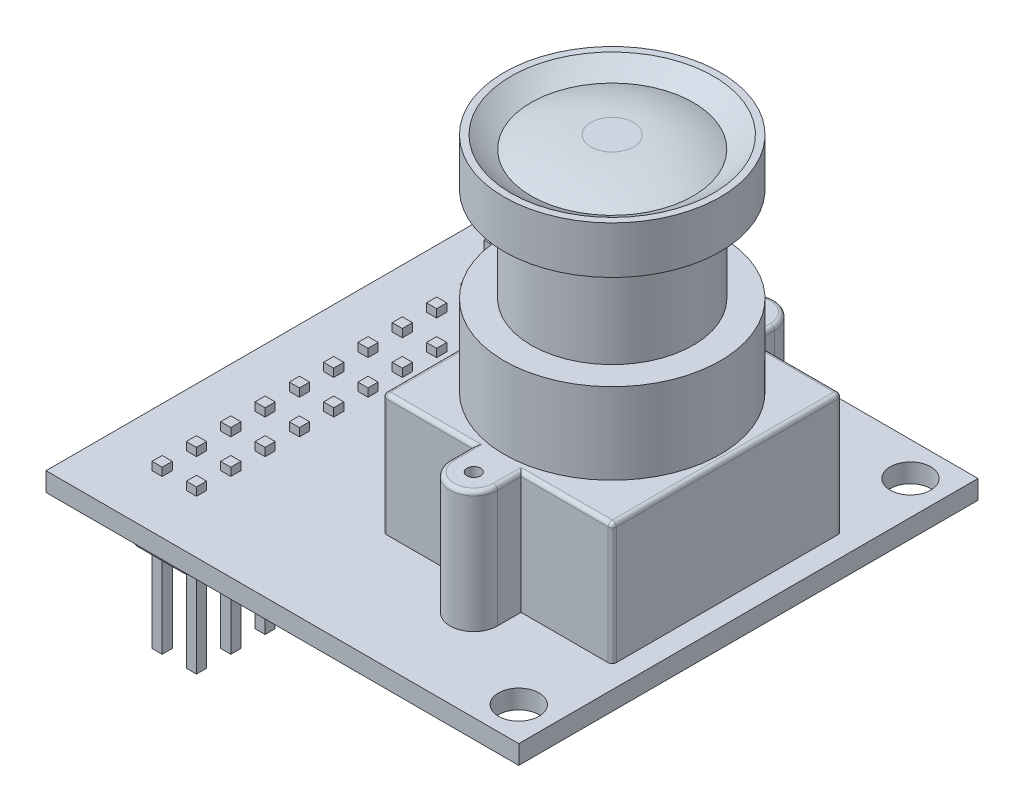
SolidWorks part; units mm, degrees
ref_plane "Front Plane" through (0, 0, 0) normal (0, 0, 1) x (1, 0, 0)
ref_plane "Top Plane" through (0, 0, 0) normal (0, 1, 0) x (1, 0, 0)
ref_plane "Right Plane" through (0, 0, 0) normal (1, 0, 0) x (0, 0, -1)
sketch "Sketch1" plane through (0, 0, 0) normal (0, 1, 0) x (1, 0, 0)
  line L1 (-19.2335, 8.5) -> (15.7665, 8.5)
  line L2 (-19.2335, 8.5) -> (-19.2335, -25.5)
  line L3 (-19.2335, -25.5) -> (15.7665, -25.5)
  line L4 (15.7665, 8.5) -> (15.7665, -25.5)
  circle A2 centre (13.2665, 6) radius 1.5
  circle A3 centre (13.2665, -23) radius 1.5
  dimension "D1" = 35
  dimension "D2" = 34
  dimension "D6" = 2.5
  dimension "D7" = 2.5
  dimension "D8" = 2.5
  dimension "D9" = 2.5
extrude "Boss-Extrude1" add sketch "Sketch1" along normal blind 1.4
sketch "Sketch2" plane through (0, 1.4, 0) normal (0, 1, 0) x (1, 0, 0)
  line L0 (15.7665, -25.5) -> (15.7665, 8.5) construction
  line L1 (-2.8135, 0) -> (3.9365, 0)
  line L2 (-2.8135, 0) -> (-2.8135, -17)
  line L3 (-2.8135, -17) -> (3.9365, -17)
  line L4 (14.1865, 0) -> (14.1865, -17)
  line L5 (-19.2335, -25.5) -> (15.7665, -25.5) construction
  line L6 (3.1865, -14.9296) -> (3.1865, -19.9748) construction
  line L7 (8.1865, -14.9296) -> (8.1865, -19.9748) construction
  line L8 (3.9365, -18.75) -> (3.9365, -17)
  line L9 (7.4365, -18.75) -> (7.4365, -17)
  line L10 (7.4365, -17) -> (14.1865, -17)
  line L11 (-2.8135, -8.5) -> (14.1865, -8.5) construction
  line L12 (7.4365, 1.75) -> (7.4365, 0)
  line L13 (3.9365, 1.75) -> (3.9365, 0)
  line L14 (7.4365, 0) -> (14.1865, 0)
  arc A0 (3.9365, -18.75) -> (7.4365, -18.75) centre (5.6865, -18.75) ccw
  arc A1 (3.9365, 1.75) -> (7.4365, 1.75) centre (5.6865, 1.75) cw
  circle A2 centre (5.6865, 1.75) radius 0.5
  circle A3 centre (5.6865, -18.75) radius 0.5
  dimension "D7" = 3.5
  dimension "D8" = 1
  dimension "D9" = 1
  dimension "D1" = 17
  dimension "D2" = 17
  dimension "D3" = 1.58
  dimension "D4" = 8.5
  dimension "D5" = 6
  dimension "D6" = 6
  dimension "D10" = 8.5
extrude "Boss-Extrude2" add sketch "Sketch2" along normal blind 9
sketch "Sketch3" plane through (0, 10.4, 0) normal (0, 1, 0) x (1, 0, 0)
  line L0 (5.6865, -8.5) -> (-7.3938, -8.5) construction
  line L1 (-2.8135, 0) -> (-2.8135, -17) construction
  line L2 (-2.8135, -9.5) -> (-2.2507, -9.5)
  line L3 (-2.8135, -9.5) -> (-2.8135, -7.5)
  line L4 (-2.8135, -7.5) -> (-2.2507, -7.5)
  line L6 (7.4365, -17) -> (14.1865, -17) construction
  line L7 (14.1865, 0) -> (7.4365, 0) construction
  arc A0 (-2.2507, -9.5) -> (-2.2507, -7.5) centre (5.6865, -8.5) ccw
  circle A1 centre (5.6865, -18.75) radius 0.5 construction
  dimension "D1" = 16
  dimension "D2" = 1
  dimension "D3" = 8.5
  dimension "D4" = 8.5
  dimension "D5" = 1
  dimension "D6" = 0
extrude "Boss-Extrude3" add sketch "Sketch3" along normal blind 6
sketch "Sketch4" plane through (0, 16.4, 0) normal (0, 1, 0) x (1, 0, 0)
  circle A0 centre (5.6865, -8.5) radius 6
  dimension "D1" = 12
extrude "Boss-Extrude4" add sketch "Sketch4" along normal blind 7
sketch "Sketch5" plane through (0, 23.4, 0) normal (0, 1, 0) x (1, 0, 0)
  circle A0 centre (5.6865, -8.5) radius 8
  dimension "D1" = 16
extrude "Boss-Extrude5" add sketch "Sketch5" along normal blind 3.5
sketch "Sketch6" plane through (0, 26.9, 0) normal (0, 1, 0) x (1, 0, 0)
  circle A0 centre (5.6865, -8.5) radius 7.5
  dimension "D1" = 15
extrude "Cut-Extrude1" cut sketch "Sketch6" against normal blind 2
fillet "Fillet1" radius 10 1 edges at (5.6865, 24.9, 16)
sketch "Sketch7" plane through (0, 24.9, 0) normal (0, 1, 0) x (1, 0, 0)
  circle A0 centre (5.6865, -8.5) radius 6
  dimension "D1" = 12
extrude "Boss-Extrude6" add sketch "Sketch7" along normal blind 2
fillet "Fillet2" radius 11 1 edges at (5.6865, 26.9, 14.5)
fillet "Fillet3" radius 0.3 17 edges at (0.5615, 10.4, 0) (3.9365, 10.4, -0.875) (5.6865, 10.4, -3.5) (7.4365, 10.4, -0.875) (10.8115, 10.4, 0) (14.1865, 10.4, 8.5) (10.8115, 10.4, 17) (7.4365, 10.4, 17.875) (5.6865, 10.4, 20.5) (3.9365, 10.4, 17.875) (0.5615, 10.4, 17) (-2.8135, 10.4, 13.25) (-2.8135, 10.4, 3.75) (-2.8135, 5.9, 0) (-2.8135, 5.9, 17) (14.1865, 5.9, 0) (14.1865, 5.9, 17)
sketch "Sketch8" plane through (-2.8135, 0, 0) normal (-1, 0, 0) x (0, 0, 1)
  line L0 (7.5, 16.4) -> (7.5, 10.1) construction
  line L1 (9.5, 16.4) -> (9.5, 10.1) construction
  line L2 (7.5, 16.4) -> (9.5, 16.4) construction
  circle A0 centre (8.5, 13.9) radius 0.5
  dimension "D1" = 1
  dimension "D2" = 1
  dimension "D3" = 1
  dimension "D4" = 2.5
extrude "Cut-Extrude2" cut sketch "Sketch8" against normal blind 0.5
sketch "Sketch9" plane through (0, 0, 0) normal (0, -1, 0) x (1, 0, 0)
  line L0 (-14.9335, 21.2) -> (-14.9335, 22.1314) construction
  line L1 (-12.0185, 20.825) -> (-12.0185, 21.575)
  line L2 (-14.5585, 20.825) -> (-15.3085, 20.825)
  line L3 (-14.5585, 20.825) -> (-14.5585, 21.575)
  line L4 (-14.5585, 21.575) -> (-15.3085, 21.575)
  line L5 (-15.3085, 20.825) -> (-15.3085, 21.575)
  line L6 (-14.5585, 20.825) -> (-15.3085, 21.575) construction
  line L7 (-14.5585, 21.575) -> (-15.3085, 20.825) construction
  line L8 (-12.0185, 21.575) -> (-12.7685, 21.575)
  line L9 (-12.7685, 20.825) -> (-12.7685, 21.575)
  line L10 (-12.0185, 20.825) -> (-12.7685, 20.825)
  line L11 (-19.2335, -8.5) -> (-19.2335, 25.5) construction
  line L12 (-19.2335, 25.5) -> (15.7665, 25.5) construction
  line L13 (-12.0185, 18.285) -> (-12.0185, 19.035)
  line L14 (-12.0185, 19.035) -> (-12.7685, 19.035)
  line L15 (-12.7685, 18.285) -> (-12.7685, 19.035)
  line L16 (-12.0185, 18.285) -> (-12.7685, 18.285)
  line L17 (-12.0185, 15.745) -> (-12.0185, 16.495)
  line L18 (-12.0185, 16.495) -> (-12.7685, 16.495)
  line L19 (-12.7685, 15.745) -> (-12.7685, 16.495)
  line L20 (-12.0185, 15.745) -> (-12.7685, 15.745)
  line L21 (-12.0185, 13.205) -> (-12.0185, 13.955)
  line L22 (-12.0185, 13.955) -> (-12.7685, 13.955)
  line L23 (-12.7685, 13.205) -> (-12.7685, 13.955)
  line L24 (-12.0185, 13.205) -> (-12.7685, 13.205)
  line L25 (-12.0185, 10.665) -> (-12.0185, 11.415)
  line L26 (-12.0185, 11.415) -> (-12.7685, 11.415)
  line L27 (-12.7685, 10.665) -> (-12.7685, 11.415)
  line L28 (-12.0185, 10.665) -> (-12.7685, 10.665)
  line L29 (-12.0185, 8.125) -> (-12.0185, 8.875)
  line L30 (-12.0185, 8.875) -> (-12.7685, 8.875)
  line L31 (-12.7685, 8.125) -> (-12.7685, 8.875)
  line L32 (-12.0185, 8.125) -> (-12.7685, 8.125)
  line L33 (-12.0185, 5.585) -> (-12.0185, 6.335)
  line L34 (-12.0185, 6.335) -> (-12.7685, 6.335)
  line L35 (-12.7685, 5.585) -> (-12.7685, 6.335)
  line L36 (-12.0185, 5.585) -> (-12.7685, 5.585)
  line L37 (-12.0185, 3.045) -> (-12.0185, 3.795)
  line L38 (-12.0185, 3.795) -> (-12.7685, 3.795)
  line L39 (-12.7685, 3.045) -> (-12.7685, 3.795)
  line L40 (-12.0185, 3.045) -> (-12.7685, 3.045)
  line L41 (-12.0185, 0.505) -> (-12.0185, 1.255)
  line L42 (-12.0185, 1.255) -> (-12.7685, 1.255)
  line L43 (-12.7685, 0.505) -> (-12.7685, 1.255)
  line L44 (-12.0185, 0.505) -> (-12.7685, 0.505)
  line L45 (-12.0185, -2.035) -> (-12.0185, -1.285)
  line L46 (-12.0185, -1.285) -> (-12.7685, -1.285)
  line L47 (-12.7685, -2.035) -> (-12.7685, -1.285)
  line L48 (-12.0185, -2.035) -> (-12.7685, -2.035)
  line L49 (-12.0185, -4.575) -> (-12.0185, -3.825)
  line L50 (-12.0185, -3.825) -> (-12.7685, -3.825)
  line L51 (-12.7685, -4.575) -> (-12.7685, -3.825)
  line L52 (-12.0185, -4.575) -> (-12.7685, -4.575)
  line L53 (-14.5585, 18.285) -> (-14.5585, 19.035)
  line L54 (-14.5585, 19.035) -> (-15.3085, 19.035)
  line L55 (-15.3085, 18.285) -> (-15.3085, 19.035)
  line L56 (-14.5585, 18.285) -> (-15.3085, 18.285)
  line L57 (-14.5585, 15.745) -> (-14.5585, 16.495)
  line L58 (-14.5585, 16.495) -> (-15.3085, 16.495)
  line L59 (-15.3085, 15.745) -> (-15.3085, 16.495)
  line L60 (-14.5585, 15.745) -> (-15.3085, 15.745)
  line L61 (-14.5585, 13.205) -> (-14.5585, 13.955)
  line L62 (-14.5585, 13.955) -> (-15.3085, 13.955)
  line L63 (-15.3085, 13.205) -> (-15.3085, 13.955)
  line L64 (-14.5585, 13.205) -> (-15.3085, 13.205)
  line L65 (-14.5585, 10.665) -> (-14.5585, 11.415)
  line L66 (-14.5585, 11.415) -> (-15.3085, 11.415)
  line L67 (-15.3085, 10.665) -> (-15.3085, 11.415)
  line L68 (-14.5585, 10.665) -> (-15.3085, 10.665)
  line L69 (-14.5585, 8.125) -> (-14.5585, 8.875)
  line L70 (-14.5585, 8.875) -> (-15.3085, 8.875)
  line L71 (-15.3085, 8.125) -> (-15.3085, 8.875)
  line L72 (-14.5585, 8.125) -> (-15.3085, 8.125)
  line L73 (-14.5585, 5.585) -> (-14.5585, 6.335)
  line L74 (-14.5585, 6.335) -> (-15.3085, 6.335)
  line L75 (-15.3085, 5.585) -> (-15.3085, 6.335)
  line L76 (-14.5585, 5.585) -> (-15.3085, 5.585)
  line L77 (-14.5585, 3.045) -> (-14.5585, 3.795)
  line L85 (-14.5585, 3.795) -> (-15.3085, 3.795)
  line L86 (-15.3085, 3.045) -> (-15.3085, 3.795)
  line L87 (-14.5585, 3.045) -> (-15.3085, 3.045)
  line L88 (-14.5585, 0.505) -> (-14.5585, 1.255)
  line L89 (-14.5585, 1.255) -> (-15.3085, 1.255)
  line L90 (-15.3085, 0.505) -> (-15.3085, 1.255)
  line L91 (-14.5585, 0.505) -> (-15.3085, 0.505)
  line L92 (-14.5585, -2.035) -> (-14.5585, -1.285)
  line L93 (-14.5585, -1.285) -> (-15.3085, -1.285)
  line L94 (-15.3085, -2.035) -> (-15.3085, -1.285)
  line L95 (-14.5585, -2.035) -> (-15.3085, -2.035)
  line L96 (-14.5585, -4.575) -> (-14.5585, -3.825)
  line L97 (-14.5585, -3.825) -> (-15.3085, -3.825)
  line L98 (-15.3085, -4.575) -> (-15.3085, -3.825)
  line L99 (-14.5585, -4.575) -> (-15.3085, -4.575)
  dimension "D2" = 0.75
  dimension "D3" = 2
  dimension "D4" = 11
  dimension "D9" = 4.3
  dimension "D10" = 4.3
extrude "Boss-Extrude7" add sketch "Sketch9" along normal blind 10 and the other way blind 2
sketch "Sketch10" plane through (0, 0, 0) normal (0, -1, 0) x (1, 0, 0)
  line L0 (-12.7685, 21.575) -> (-12.0185, 21.575) construction
  line L1 (-16.3085, 22.575) -> (-11.0185, 22.575)
  line L2 (-16.3085, 22.575) -> (-16.3085, -5.575)
  line L3 (-16.3085, -5.575) -> (-11.0185, -5.575)
  line L4 (-11.0185, 22.575) -> (-11.0185, -5.575)
  line L5 (-15.3085, 20.825) -> (-15.3085, 21.575) construction
  line L6 (-12.0185, 21.575) -> (-12.0185, 20.825) construction
  line L7 (-12.7685, -4.575) -> (-12.0185, -4.575) construction
  dimension "D1" = 1
  dimension "D2" = 1
  dimension "D3" = 1
  dimension "D4" = 1
extrude "Boss-Extrude8" add sketch "Sketch10" along normal blind 3
fillet "Fillet4" radius 1 4 edges at (-16.3085, -1.5, -5.575) (-11.0185, -1.5, -5.575) (-11.0185, -1.5, 22.575) (-16.3085, -1.5, 22.575)
